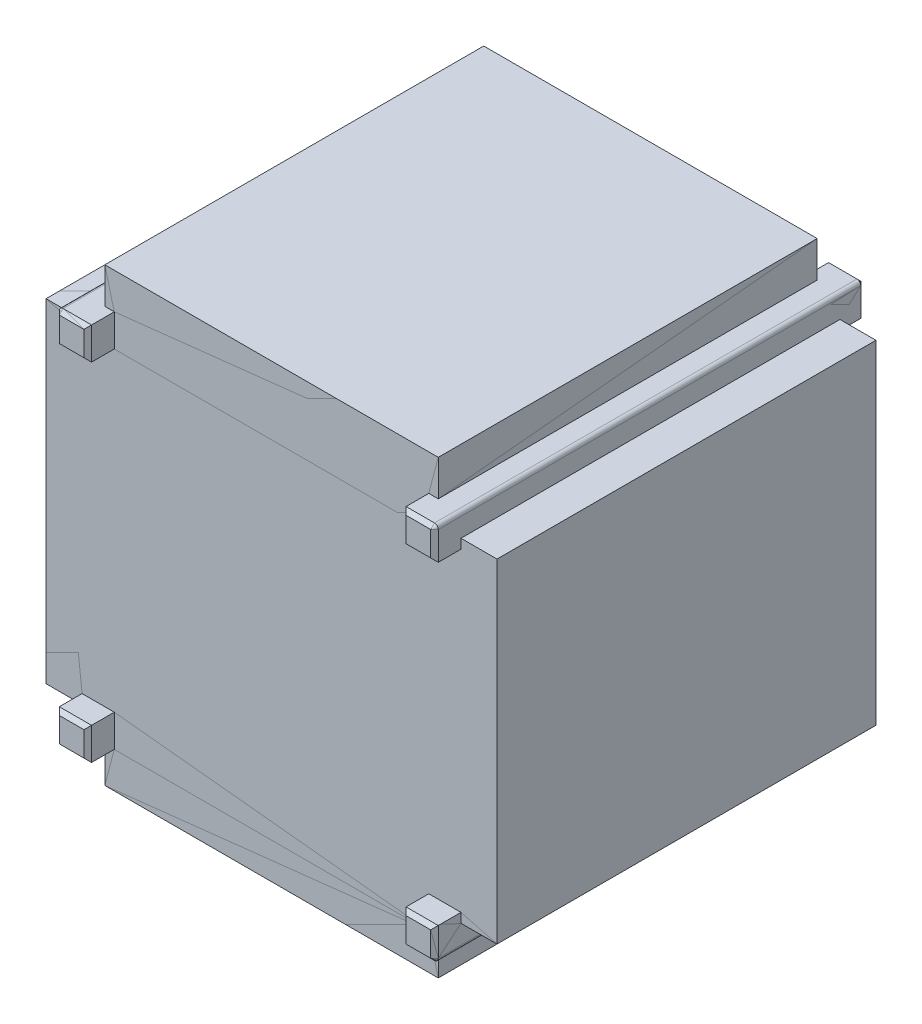
SolidWorks part; units mm, degrees
ref_plane "Front Plane" through (0, 0, 0) normal (0, 0, 1) x (1, 0, 0)
ref_plane "Top Plane" through (0, 0, 0) normal (0, 1, 0) x (1, 0, 0)
ref_plane "Right Plane" through (0, 0, 0) normal (1, 0, 0) x (0, 0, -1)
sketch "Sketch1" plane through (0, 0, 0) normal (0, 0, 1) x (1, 0, 0)
  line L1 (-50, -50) -> (50, -50) construction
  line L2 (-50, -50) -> (-50, 50) construction
  line L3 (-50, 50) -> (50, 50) construction
  line L4 (50, -50) -> (50, 50) construction
  line L5 (-50, -50) -> (50, 50) construction
  line L6 (-50, 50) -> (50, -50) construction
  line L23 (-50, 50) -> (-41.5, 50)
  line L24 (-50, 50) -> (-50, 41.5)
  line L25 (-50, 41.5) -> (-41.5, 41.5)
  line L26 (-41.5, 50) -> (-41.5, 41.5)
  line L27 (50, 50) -> (41.5, 50)
  line L28 (50, 50) -> (50, 41.5)
  line L29 (50, 41.5) -> (41.5, 41.5)
  line L30 (41.5, 50) -> (41.5, 41.5)
  line L31 (50, -50) -> (41.5, -50)
  line L32 (50, -50) -> (50, -41.5)
  line L33 (50, -41.5) -> (41.5, -41.5)
  line L34 (41.5, -50) -> (41.5, -41.5)
  line L35 (-50, -50) -> (-41.5, -50)
  line L36 (-50, -50) -> (-50, -41.5)
  line L37 (-50, -41.5) -> (-41.5, -41.5)
  line L38 (-41.5, -50) -> (-41.5, -41.5)
  point P0 (0, 0)
  dimension "D1" = 100
  dimension "D2" = 100
  dimension "D3" = 8.5
extrude "Boss-Extrude1" add sketch "Sketch1" along normal blind 56.75 and the other way blind 56.75
sketch "Sketch2" plane through (0, 0, 0) normal (0, 0, 1) x (1, 0, 0)
  line L1 (-50, -50) -> (50, -50) construction
  line L2 (-50, -50) -> (-50, 50) construction
  line L3 (-50, 50) -> (50, 50) construction
  line L4 (50, -50) -> (50, 50) construction
  line L5 (-50, -50) -> (50, 50) construction
  line L6 (-50, 50) -> (50, -50) construction
  line L21 (-65.5532, 0) -> (65.5532, 0) construction
  line L28 (-44, 50) -> (-44, 59.5)
  line L29 (-44, 59.5) -> (44, 59.5)
  line L30 (44, 59.5) -> (44, 50)
  line L31 (44, 50) -> (50, 50)
  line L32 (50, 50) -> (50, 44)
  line L33 (50, 44) -> (59.5, 44)
  line L34 (59.5, 44) -> (59.5, -44)
  line L35 (59.5, -44) -> (50, -44)
  line L36 (50, -44) -> (50, -50)
  line L37 (50, -50) -> (44, -50)
  line L38 (44, -50) -> (44, -59.5)
  line L39 (44, -59.5) -> (-44, -59.5)
  line L40 (-44, -59.5) -> (-44, -50)
  line L41 (-44, -50) -> (-50, -50)
  line L42 (-50, -50) -> (-50, -44)
  line L43 (-50, -44) -> (-59.5, -44)
  line L44 (-59.5, -44) -> (-59.5, 44)
  line L45 (-59.5, 44) -> (-50, 44)
  line L46 (-50, 44) -> (-50, 50)
  line L47 (-50, 50) -> (-44, 50)
  point P0 (0, 0)
  point P21 (-59.5, 0)
  point P26 (0, 0)
  point P27 (59.5, 0)
  point P28 (0, 59.5)
  point P29 (0, 0)
  point P30 (0, -59.5)
  dimension "D1" = 88
  dimension "D2" = 88
  dimension "D3" = 119
  dimension "D4" = 119
extrude "Boss-Extrude2" add sketch "Sketch2" along normal blind 49.75 and the other way blind 50.25
fillet "Fillet1" radius 1 4 edges at (-50, -50, 0) (50, 50, 0) (50, -50, 0) (-50, 50, 0)
chamfer "Chamfer2" distance 1 angle 45 40 edges at (-45.75, -41.5, 56.75) (-41.5, -45.75, 56.75) (-45.25, -50, 56.75) (-49.7071, -49.7071, 56.75) (-50, -45.25, 56.75) (41.5, -45.75, 56.75) (45.75, -41.5, 56.75) (45.75, 41.5, 56.75) (41.5, 45.75, 56.75) (45.25, 50, 56.75) (49.7071, 49.7071, 56.75) (50, 45.25, 56.75) (-41.5, 45.75, 56.75) (-45.75, 41.5, 56.75) (41.5, 45.75, -56.75) (45.75, 41.5, -56.75) (50, 45.25, -56.75) (49.7071, 49.7071, -56.75) (45.25, 50, -56.75) (-45.75, 41.5, -56.75) (-41.5, 45.75, -56.75) (-41.5, -45.75, -56.75) (-45.75, -41.5, -56.75) (-50, -45.25, -56.75) (-49.7071, -49.7071, -56.75) (-45.25, -50, -56.75) (45.75, -41.5, -56.75) (41.5, -45.75, -56.75) (45.25, -50, 56.75) (50, -45.25, 56.75) (-45.25, 50, 56.75) (-50, 45.25, 56.75) (-45.25, 50, -56.75) (-50, 45.25, -56.75) (45.25, -50, -56.75) (50, -45.25, -56.75) (49.7071, -49.7071, 56.75) (-49.7071, 49.7071, 56.75) (-49.7071, 49.7071, -56.75) (49.7071, -49.7071, -56.75)
surface "Surface-Offset1" parameters "D1"=0
equation "\"D1@Boss-Extrude1\"=113.5/2mm"
equation "\"D2@Boss-Extrude1\"=113.5/2"
